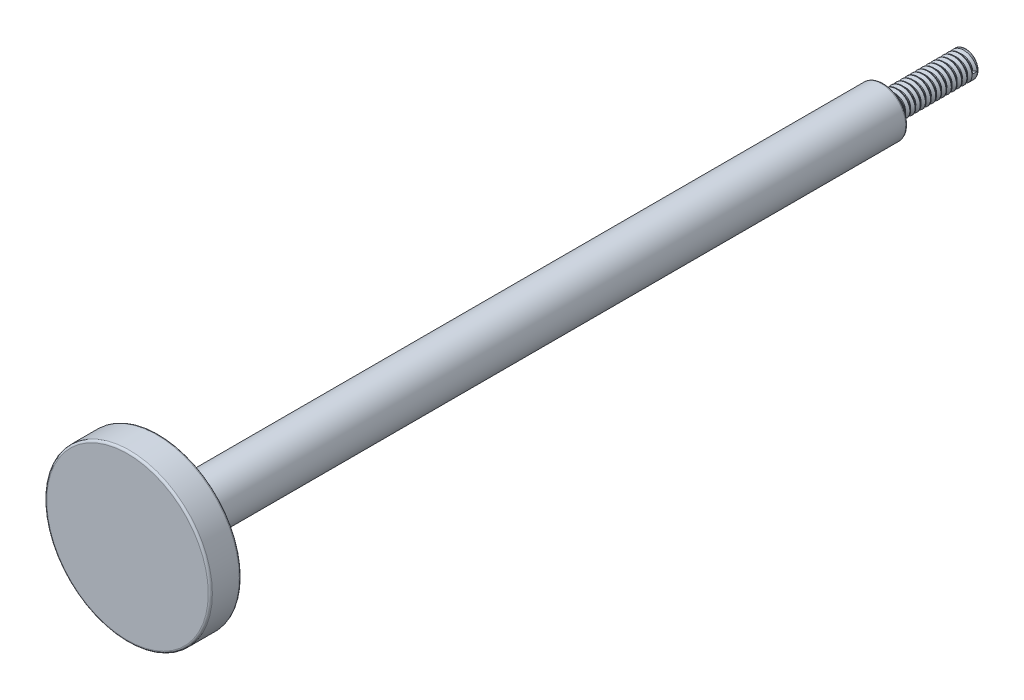
SolidWorks part; units mm, degrees
ref_plane "Front Plane" through (0, 0, 0) normal (0, 0, 1) x (1, 0, 0)
ref_plane "Top Plane" through (0, 0, 0) normal (0, 1, 0) x (1, 0, 0)
ref_plane "Right Plane" through (0, 0, 0) normal (1, 0, 0) x (0, 0, -1)
sketch "Sketch1" plane through (0, 0, 0) normal (0, 0, 1) x (1, 0, 0)
  circle A0 centre (0, 0) radius 2.35
  dimension "D1" = 4.7
extrude "Boss-Extrude1" add sketch "Sketch1" along normal blind 70
sketch "Sketch2" plane through (0, 0, 70) normal (0, 0, 1) x (1, 0, 0)
  circle A0 centre (0, 0) radius 8
  dimension "D1" = 16
extrude "Boss-Extrude2" add sketch "Sketch2" along normal blind 3
sketch "Sketch11" plane through (0, 0, 0) normal (0, 0, -1) x (-1, 0, 0)
  circle A0 centre (0, 0) radius 1.25
  dimension "D1" = 2.5
extrude "Boss-Extrude3" add sketch "Sketch11" along normal blind 8
fillet "Fillet1" radius 0.2 1 edges at (-1.25, 0, -8)
thread "Thread1" pitch 0.5 method cut profile "Thread Profile1" start angle 0, offset 0, length 0, pitch 0.5, diameter 2.5
ref_plane "Plane1" through (1.25, 0, -7.8) normal (0, -1, 0) x (1, 0, 0)
sketch "Thread Profile1" plane through (1.25, 0, -7.8) normal (0, -1, 0) x (1, 0, 0)
  line L0 (0, 0) -> (0, 0.5) construction
  line L11 (0, 0) -> (0, 0.4375)
  line L12 (0, 0.4375) -> (-0.2706, 0.2812)
  line L13 (-0.2706, 0.2812) -> (-0.2706, 0.1562)
  line L15 (-0.2706, 0.1562) -> (0, 0)
  line L17 (-0.2706, 0.2187) -> (0, 0.2187) construction
  point P2 (0, 0)
  dimension "Pitch" = 0.5
  dimension "Profile_Angle" = 60
  dimension "Profile_Land" = 0.125
  dimension "Profile_Height" = 0.2706
fillet "Fillet2" radius 0.2 4 edges at (8, 0, 73) (8, 0, 70) (2.35, 0, 70) (2.35, 0, 0)
